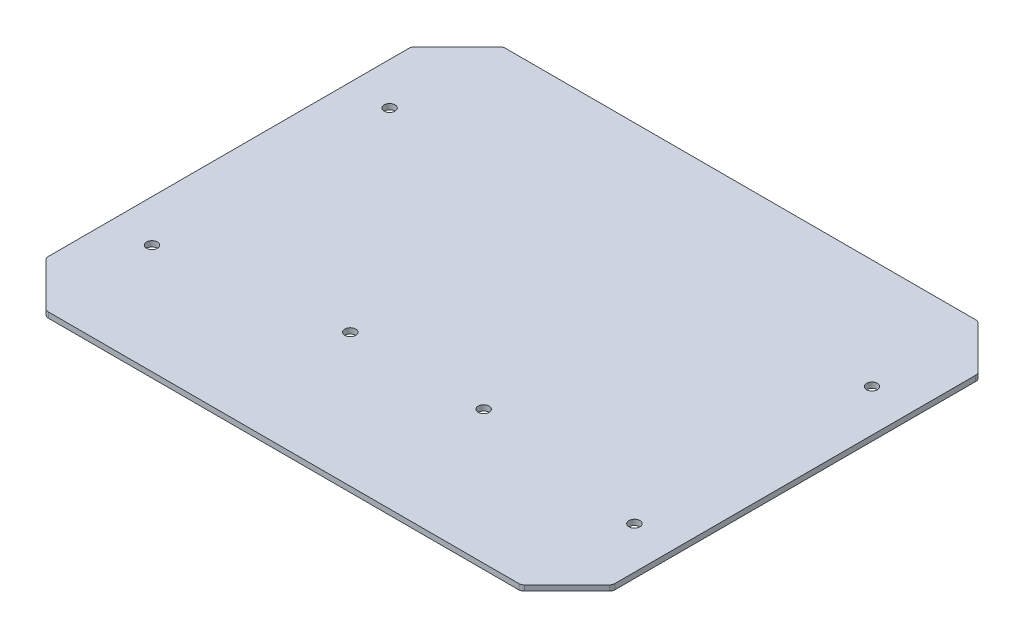
SolidWorks part; units mm, degrees
ref_plane "Plan de face" through (0, 0, 0) normal (0, 0, 1) x (1, 0, 0)
ref_plane "Plan de dessus" through (0, 0, 0) normal (0, 1, 0) x (1, 0, 0)
ref_plane "Plan de droite" through (0, 0, 0) normal (1, 0, 0) x (0, 0, -1)
sketch "Esquisse1" plane through (0, 0, 0) normal (0, 1, 0) x (1, 0, 0)
  line L0 (0, 125) -> (0, -125) construction
  line L1 (-155, 0) -> (155, 0) construction
  line L2 (-130, 125) -> (130, 125)
  line L3 (-130, -125) -> (130, -125)
  line L4 (-155, 100) -> (-155, -100)
  line L5 (155, 100) -> (155, -100)
  line L6 (-155, 100) -> (-130, 125)
  line L7 (-155, -100) -> (-130, -125)
  line L8 (130, -125) -> (155, -100)
  line L9 (130, 125) -> (155, 100)
  point P3 (0, 0)
  point P6 (0, 0)
  point P8 (0, 125)
  point P11 (0, -125)
  point P14 (-155, 0)
  point P17 (155, 0)
  dimension "D1" = 310
  dimension "D2" = 250
  dimension "D3" = 135
  dimension "D4" = 260
  dimension "D5" = 200
extrude "Boss.-Extru.1" add sketch "Esquisse1" along normal blind 3
fillet "Congé1" radius 3 8 edges at (-130, 1.5, 125) (-155, 1.5, 100) (130, 1.5, 125) (155, 1.5, 100) (155, 1.5, -100) (130, 1.5, -125) (-130, 1.5, -125) (-155, 1.5, -100)
sketch "Esquisse2" plane through (0, 3, 0) normal (0, 1, 0) x (1, 0, 0)
  line L0 (0, 125) -> (0, -125) construction
  line L1 (128.7574, 125) -> (-128.7574, 125) construction
  line L2 (-128.7574, -125) -> (128.7574, -125) construction
  line L3 (-155, 0) -> (155, 0) construction
  line L4 (-155, 98.7574) -> (-155, -98.7574) construction
  line L5 (155, -98.7574) -> (155, 98.7574) construction
  line L6 (-132, 65) -> (-132, 0) construction
  line L7 (-132, 65) -> (-155, 65) construction
  circle A0 centre (-132, 65) radius 3
  circle A1 centre (-132, -65) radius 3
  circle A2 centre (132, -65) radius 3
  circle A3 centre (132, 65) radius 3
  dimension "D1" = 6
  dimension "D2" = 23
  dimension "D3" = 65
extrude "Perçage Profilé" cut sketch "Esquisse2" against normal through all
sketch "Esquisse3" plane through (0, 3, 0) normal (0, 1, 0) x (1, 0, 0)
  line L0 (0, -125) -> (0, -52) construction
  line L1 (-128.7574, -125) -> (128.7574, -125) construction
  line L2 (-36.5, -52) -> (36.5, -52) construction
  circle A0 centre (-36.5, -52) radius 3
  circle A1 centre (36.5, -52) radius 3
  point P8 (0, -52)
  dimension "D1" = 6
  dimension "D2" = 73
  dimension "D3" = 73
extrude "Enlèv. mat.-Extru.1" cut sketch "Esquisse3" against normal through all
